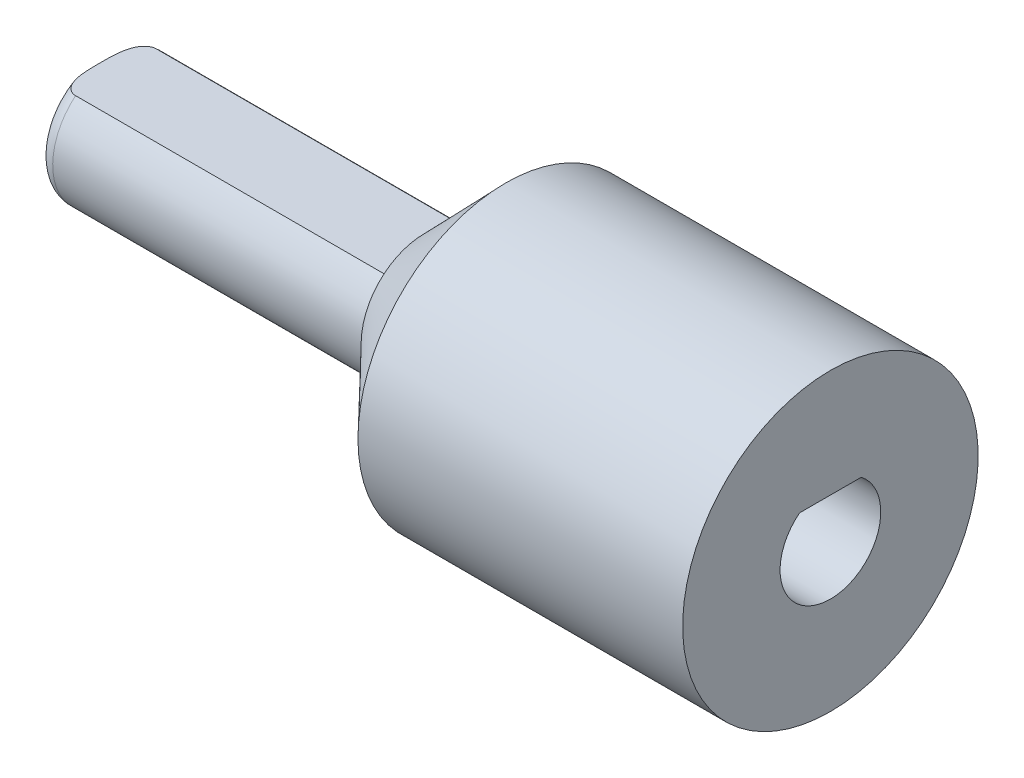
SolidWorks part; units mm, degrees
material "ABS"
ref_plane "Plan de face" through (0, 0, 0) normal (0, 0, 1) x (1, 0, 0)
ref_plane "Plan de dessus" through (0, 0, 0) normal (0, 1, 0) x (1, 0, 0)
ref_plane "Plan de droite" through (0, 0, 0) normal (1, 0, 0) x (0, 0, -1)
sketch "Esquisse2" plane through (0, 0, 0) normal (0, 0, 1) x (1, 0, 0)
  line L0 (0, 0) -> (0, 3.9)
  line L1 (0, 3.9) -> (25, 3.9)
  line L2 (25, 3.9) -> (25, 9.1)
  line L3 (25, 9.1) -> (45, 9.1)
  line L4 (45, 9.1) -> (45, 3.1)
  line L5 (32, 3.1) -> (45, 3.1)
  line L7 (30, 0) -> (0, 0)
  line L9 (32, 3.1) -> (30, 0)
  dimension "D1" = 3.9
  dimension "D2" = 3.1
  dimension "D3" = 2
  dimension "D4" = 25
  dimension "D5" = 20
  dimension "D6" = 13
  dimension "D7" = 6
revolve "Révolution1" add sketch "Esquisse2" angle 360 about L7
sketch "Esquisse3" plane through (0, 0, 0) normal (0, 0, 1) x (1, 0, 0)
  line L0 (25, 3.9) -> (20, 3.9)
  line L1 (25, 3.9) -> (0, 3.9) construction
  line L2 (20, 3.9) -> (25, 9.1)
  line L3 (25, 9.1) -> (25, 3.9)
  line L4 (0, 0) -> (45, 0) construction
  line L5 (45, -9.1) -> (45, 9.1) construction
  dimension "D1" = 5
revolve "Révolution2" add sketch "Esquisse3" angle 360 about L4
sketch "Esquisse4" plane through (45, 0, 0) normal (1, 0, 0) x (0, 0, -1)
  line L0 (0, -3.1) -> (0, 2.45) construction
  line L1 (-1.8993, 2.45) -> (1.8993, 2.45)
  circle A0 centre (0, 0) radius 3.1 construction
  arc A1 (-1.8993, 2.45) -> (1.8993, 2.45) centre (0, 0) cw
  point P8 (0, 2.45)
  circle M3 centre (0, 0) radius 3.1
  dimension "D1" = 5.55
extrude "Boss.-Extru.1" add sketch "Esquisse4" against normal blind 15 contours L1 M3 region at (45, 2.7125, 0)
sketch "Esquisse5" plane through (0, 0, 0) normal (-1, 0, 0) x (0, 0, 1)
  line L0 (0, 0) -> (0, 3) construction
  line L1 (-2.492, 3) -> (2.492, 3)
  circle A0 centre (0, 0) radius 3.9 construction
  arc A1 (-2.492, 3) -> (2.492, 3) centre (0, 0) ccw
  point P8 (0, 3)
  circle M2 centre (0, 0) radius 3.9
  dimension "D1" = 3
extrude "Enlèv. mat.-Extru.1" cut sketch "Esquisse5" against normal blind 20 contours L1 M2 region at (0, 3.3638, 0)
fillet "Congé2" radius 1 1 edges at (0, -3.9, 0) first distance on face at (10, -0.45, 0)
